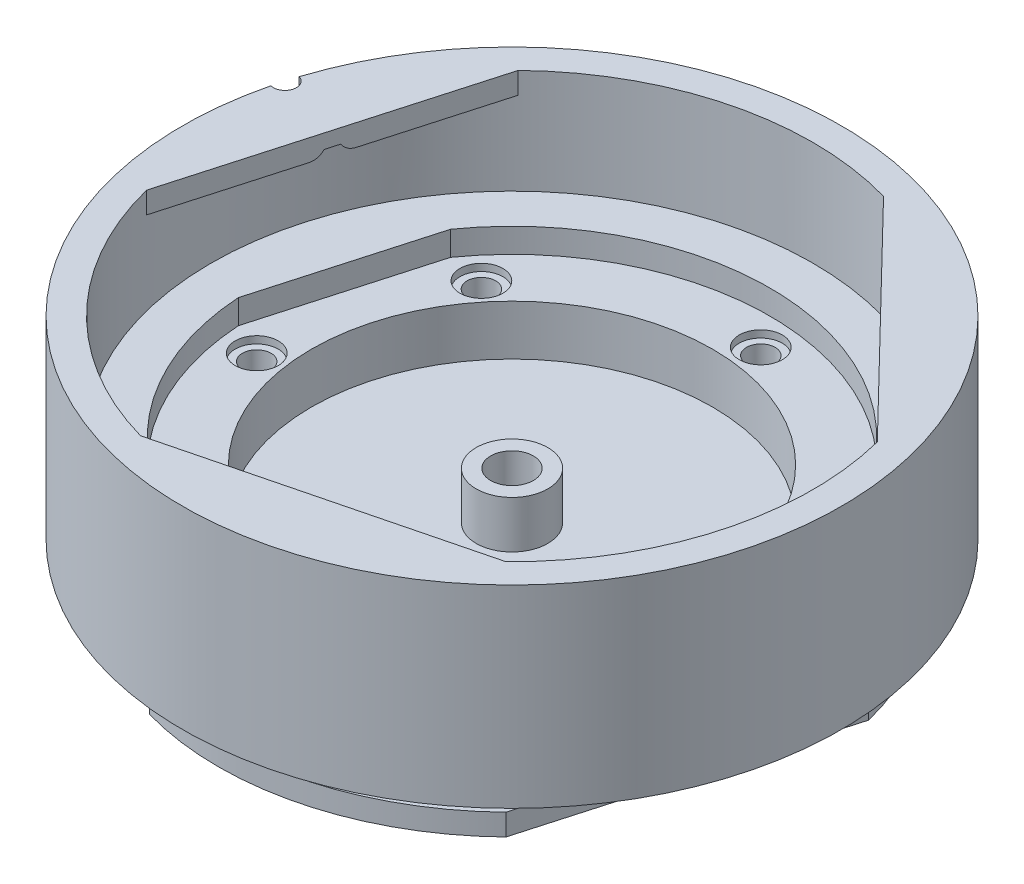
SolidWorks part; units mm, degrees
ref_plane "Front" through (0, 0, 0) normal (0, 0, 1) x (1, 0, 0)
ref_plane "Top" through (0, 0, 0) normal (0, 1, 0) x (1, 0, 0)
ref_plane "Right" through (0, 0, 0) normal (1, 0, 0) x (0, 0, -1)
sketch "Sketch1" plane through (0, 0, 0) normal (0, 1, 0) x (1, 0, 0)
  circle A0 centre (0, 0) radius 20.5
extrude "Boss-Extrude1" add sketch "Sketch1" along normal blind 1.5
sketch "Sketch2" plane through (0, 1.5, 0) normal (0, 1, 0) x (1, 0, 0)
  line L0 (-12.1923, 12.5538) -> (-12.889, 13.2712)
  line L1 (-16.9681, -4.2819) -> (-17.9377, -4.5266)
  line L2 (16.9681, 4.2819) -> (17.9377, 4.5266)
  line L3 (4.7758, 16.8357) -> (5.0487, 17.7978)
  line L4 (-4.7758, -16.8357) -> (-5.0487, -17.7978)
  line L5 (12.1923, -12.5538) -> (12.889, -13.2712)
  line L6 (-14.2824, 14.7059) -> (5.5945, 19.7219)
  line L7 (19.8769, 5.016) -> (14.2824, -14.7059)
  line L8 (-19.8769, -5.016) -> (-5.5945, -19.7219)
  line L9 (0, 0) -> (-14.2824, 14.7059) construction
  arc A0 (-19.8769, -5.016) -> (-5.5945, -19.7219) centre (0, 0) ccw
  arc A1 (-12.889, 13.2712) -> (-17.9377, -4.5266) centre (0, 0) ccw
  arc A2 (-12.1923, 12.5538) -> (-16.9681, -4.2819) centre (0, 0) ccw
  arc A3 (17.9377, 4.5266) -> (5.0487, 17.7978) centre (0, 0) ccw
  arc A4 (16.9681, 4.2819) -> (4.7758, 16.8357) centre (0, 0) ccw
  arc A5 (-5.0487, -17.7978) -> (12.889, -13.2712) centre (0, 0) ccw
  arc A6 (-4.7758, -16.8357) -> (12.1923, -12.5538) centre (0, 0) ccw
  arc A7 (14.2824, -14.7059) -> (19.8769, 5.016) centre (0, 0) ccw
  arc A8 (5.5945, 19.7219) -> (-14.2824, 14.7059) centre (0, 0) ccw
  point P13 (0, 0)
  dimension "D2" = 3
  dimension "D1" = 60
extrude "Cut-Extrude1" cut sketch "Sketch2" against normal blind 11
sketch "Sketch3" plane through (0, 1.5, 0) normal (0, 1, 0) x (1, 0, 0)
  circle A1 centre (0, 0) radius 17.5
extrude "Boss-Extrude2" add sketch "Sketch3" along normal blind 2
sketch "Sketch4" plane through (0, 3.5, 0) normal (0, 1, 0) x (1, 0, 0)
  circle A1 centre (0, 0) radius 23
extrude "Boss-Extrude3" add sketch "Sketch4" along normal blind 1
sketch "Sketch5" plane through (0, 4.5, 0) normal (0, 1, 0) x (1, 0, 0)
  circle A0 centre (0, 0) radius 23
  circle A1 centre (0, 0) radius 21
extrude "Boss-Extrude4" add sketch "Sketch5" along normal blind 11
sketch "Sketch6" plane through (0, 15.5, 0) normal (0, 1, 0) x (1, 0, 0)
  line L0 (0, 0) -> (-4.4043, 17.4529) construction
  line L2 (0, 0) -> (17.3168, -4.9122) construction
  line L5 (0, 0) -> (-12.9125, -12.5407) construction
  line L6 (14.6308, -15.0646) -> (-5.7309, -20.2029)
  line L7 (-20.3617, -5.1383) -> (-14.6308, 15.0646)
  line L8 (5.7309, 20.2029) -> (20.3617, 5.1383)
  circle A1 centre (0, 0) radius 23
  arc A4 (14.6308, -15.0646) -> (20.3617, 5.1383) centre (0, 0) ccw
  arc A5 (-20.3617, -5.1383) -> (-5.7309, -20.2029) centre (0, 0) ccw
  arc A6 (5.7309, 20.2029) -> (-14.6308, 15.0646) centre (0, 0) ccw
  point P14 (0, 0)
  point P18 (0, 0)
  point P22 (0, 0)
  dimension "D1" = 3
extrude "Boss-Extrude6" add sketch "Sketch6" along normal blind 1.5
sketch "Sketch7" plane through (0, 1.5, 0) normal (0, 1, 0) x (1, 0, 0)
  line L0 (0, 0) -> (4.2819, -16.9681) construction
  line L1 (4.0555, -18.05) -> (4.494, -20.0014)
  line L2 (4.9946, -17.813) -> (5.5346, -19.7388)
  arc A0 (-4.7758, -16.8357) -> (12.1923, -12.5538) centre (0, 0) ccw construction
  arc A1 (4.494, -20.0014) -> (5.5346, -19.7388) centre (0, 0) ccw
  arc A3 (4.0555, -18.05) -> (4.9946, -17.813) centre (0, 0) ccw
  dimension "D1" = 1.5
extrude "Boss-Extrude7" add sketch "Sketch7" along normal blind 0.8
fillet "Fillet3" radius 0.4 2 edges at (5.2646, 2.3, 18.7759) (4.2747, 2.3, 19.0257) first distance on face at (5.2646, 1.9, 18.7759) first distance on face at (4.2747, 1.9, 19.0257)
pattern_circular "CirPattern4" count 3 over 360 about axis through (0, 3.5, 0) along (0, 1, 0) of "Boss-Extrude7", "Fillet3"
ref_plane "Plane1" through (0, 15, 0) normal (0, 1, 0) x (1, 0, 0)
sketch "草图1" plane through (0, 17, 0) normal (0, 1, 0) x (1, 0, 0)
  line L0 (0, 0) -> (-12.5538, -12.1923) construction
  line L1 (0, 0) -> (-4.2819, 16.9681) construction
  line L2 (0, 0) -> (16.8357, -4.7758) construction
  circle A0 centre (0, 0) radius 18 construction
  circle A1 centre (0, 0) radius 17.5 construction
  circle A2 centre (0, 0) radius 18
  circle A3 centre (0, 0) radius 17
  point P9 (0, 0)
  dimension "D1" = 3
ref_plane "基准面1" through (0, 15, 0) normal (0, 1, 0) x (1, 0, 0)
sketch "草图9" plane through (0, 15, 0) normal (0, 1, 0) x (1, 0, 0)
  line L0 (0, 0) -> (5.016, -19.8769) construction
  line L3 (15.4424, 14.2314) -> (12.8687, 11.8595)
  line L4 (14.6764, 15.0201) -> (12.2303, 12.5167)
  arc A0 (4.494, -20.0014) -> (5.5346, -19.7388) centre (0, 0) ccw construction
  arc A5 (12.8687, 11.8595) -> (12.2303, 12.5167) centre (0, 0) ccw
  arc A6 (15.4424, 14.2314) -> (14.6764, 15.0201) centre (0, 0) ccw
  point P15 (0, 0)
extrude "切除-拉伸14" cut sketch "草图9" against normal blind 1 and the other way blind 1
fillet "圆角4" radius 1 2 edges at (14.4102, 15.5, -13.2802) (13.6954, 15.5, -14.0162)
pattern_circular "阵列(圆周)2" count 3 over 360 about axis through (0, 17, 0) along (0, 1, 0) of "切除-拉伸14", "圆角4"
sketch "草图15" plane through (0, 4.5, 0) normal (0, 1, 0) x (1, 0, 0)
  line L0 (0, 0) -> (-4.2819, 16.9681) construction
  circle A0 centre (0, 0) radius 21
  circle A5 centre (0, 0) radius 14
extrude "凸台-拉伸6" add sketch "草图15" along normal blind 3.5
sketch "草图16" plane through (0, 4.5, 0) normal (0, 1, 0) x (1, 0, 0)
  circle A0 centre (0, 0) radius 2.5
extrude "凸台-拉伸7" add sketch "草图16" along normal blind 3.3
sketch "草图17" plane through (0, 7.8, 0) normal (0, 1, 0) x (1, 0, 0)
  circle A0 centre (0, 0) radius 1.49
extrude "切除-拉伸17" cut sketch "草图17" against normal blind 32
sketch "草图20" plane through (0, 8, 0) normal (0, 1, 0) x (1, 0, 0)
  circle A0 centre (0, 0) radius 21
  circle A1 centre (0, 0) radius 18
extrude "凸台-拉伸8" add sketch "草图20" along normal blind 1.7
sketch "草图21" plane through (0, 8, 0) normal (0, 1, 0) x (1, 0, 0)
  line L0 (0, 0) -> (16.6631, -4.7268) construction
  line L2 (0, 0) -> (-7.1059, -25.0502) construction
  circle A0 centre (-15.6614, -2.1579) radius 1.5
  circle A1 centre (-6.9509, -14.2656) radius 1.5
  circle A2 centre (12.1955, -10.06) radius 1.5
  circle A3 centre (15.6614, 2.1579) radius 1.5
  circle A4 centre (1.575, 15.7905) radius 1.5
  circle A5 centre (-12.1955, 10.06) radius 1.5
  circle A6 centre (0, 0) radius 1.49 construction
  circle A7 centre (1.4334, -0.4066) radius 0.5 construction
  dimension "D1" = 14.478
  dimension "D3" = 2.794
  dimension "D5" = 14.478
  dimension "D2" = 6.35
  dimension "D4" = 15.621
  dimension "D6" = 6.35
extrude "切除-拉伸18" cut sketch "草图21" against normal blind 0.5
sketch "草图22" plane through (0, 7.5, 0) normal (0, 1, 0) x (1, 0, 0)
  line L0 (0, 0) -> (16.9497, -4.8081) construction
  circle A1 centre (-15.6614, -2.1579) radius 1
  circle A2 centre (-6.9509, -14.2656) radius 1
  circle A3 centre (12.1955, -10.06) radius 1
  circle A4 centre (15.6614, 2.1579) radius 1
  circle A5 centre (1.575, 15.7905) radius 1
  circle A6 centre (-12.1955, 10.06) radius 1
extrude "切除-拉伸19" cut sketch "草图22" against normal blind 10
sketch "草图24" plane through (0, 17, 0) normal (0, 1, 0) x (1, 0, 0)
  line L0 (0, 0) -> (-17.4962, 4.9631) construction
  circle A0 centre (-22.127, 6.2767) radius 0.8
  circle A1 centre (0, 0) radius 23 construction
extrude "切除-拉伸20" cut sketch "草图24" against normal blind 20
sketch "草图25" plane through (0, 8, 0) normal (0, 1, 0) x (1, 0, 0)
  line L0 (0, 0) -> (-25.762, 7.3079) construction
  line L1 (-14.689, 10.4035) -> (-17.9638, -1.141)
  arc A0 (-14.689, 10.4035) -> (-17.9638, -1.141) centre (0, 0) ccw
extrude "凸台-拉伸9" add sketch "草图25" along normal blind 1.7
